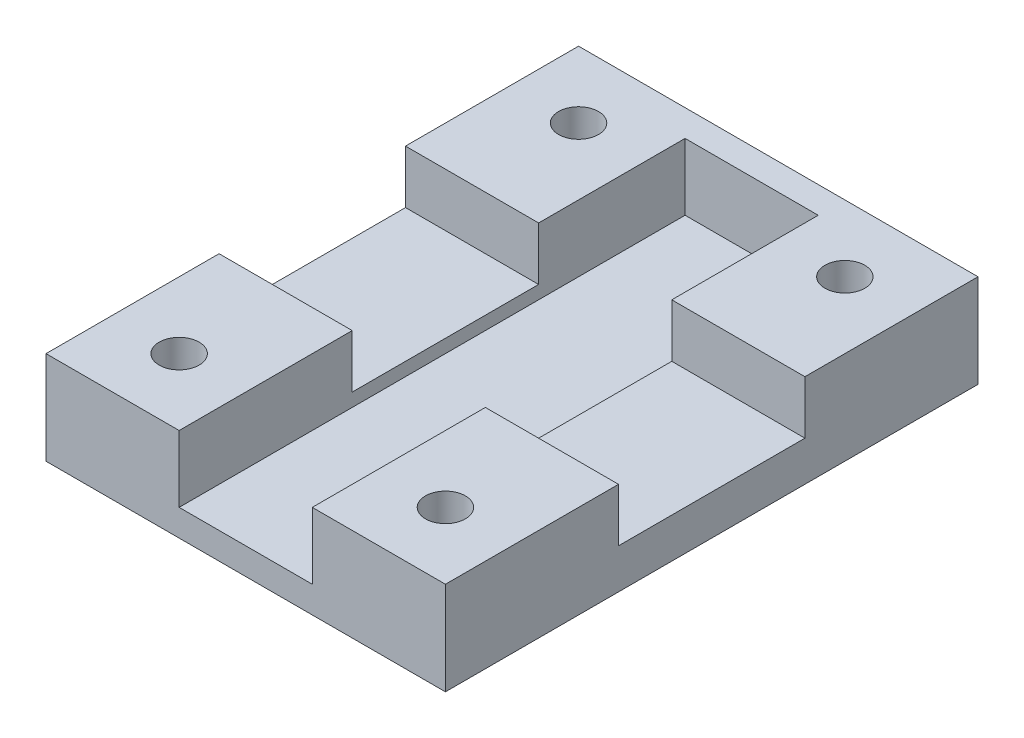
SolidWorks part; units mm, degrees
ref_plane "Plan de face" through (0, 0, 0) normal (0, 0, 1) x (1, 0, 0)
ref_plane "Plan de dessus" through (0, 0, 0) normal (0, 1, 0) x (1, 0, 0)
ref_plane "Plan de droite" through (0, 0, 0) normal (1, 0, 0) x (0, 0, -1)
sketch "Esquisse1" plane through (0, 0, 0) normal (0, 0, 1) x (1, 0, 0)
  line L0 (5, 0) -> (15, 0)
  line L1 (15, 0) -> (15, -7)
  line L2 (15, -7) -> (-15, -7)
  line L3 (-15, -7) -> (-15, 0)
  line L4 (-15, 0) -> (-5, 0)
  line L5 (5, 0) -> (5, -5)
  line L6 (5, -5) -> (-5, -5)
  line L7 (-5, -5) -> (-5, 0)
  dimension "D1" = 5
  dimension "D2" = 5
  dimension "D3" = 7
  dimension "D4" = 5
  dimension "D5" = 15
  dimension "D6" = 7
  dimension "D7" = 15
extrude "Boss.-Extru.1" add sketch "Esquisse1" along normal blind 40
sketch "Esquisse2" plane through (0, 0, 0) normal (0, 1, 0) x (1, 0, 0)
  line L0 (0, 0) -> (0, -40.0085) construction
  line L1 (-15, -20) -> (15, -20) construction
  line L2 (-15, -40) -> (-15, 0) construction
  line L3 (15, -40) -> (15, 0) construction
  circle A0 centre (-10, -5) radius 1.5
  circle A1 centre (-10, -35) radius 1.5
  circle A2 centre (10, -35) radius 1.5
  circle A3 centre (10, -5) radius 1.5
  dimension "D1" = 10
  dimension "D3" = 3
  dimension "D2" = 15
extrude "Enlèv. mat.-Extru.1" cut sketch "Esquisse2" against normal up to next
sketch "Esquisse3" plane through (0, 0, 0) normal (0, 1, 0) x (1, 0, 0)
  line L0 (0, 0) -> (0, -40) construction
  line L1 (5, -40) -> (-5, -40) construction
  line L2 (-15, -27) -> (-15, -13)
  line L3 (-15, -40) -> (-15, 0) construction
  line L4 (-15, -20) -> (15, -20) construction
  line L5 (15, -40) -> (15, 0) construction
  line L6 (-15, -13) -> (-5, -13)
  line L7 (-5, -40) -> (-5, 0) construction
  line L8 (-5, -13) -> (-5, -27)
  line L9 (-15, -27) -> (-5, -27)
  line L10 (15, -27) -> (5, -27)
  line L11 (5, -13) -> (5, -27)
  line L12 (15, -13) -> (5, -13)
  line L13 (15, -27) -> (15, -13)
  point P17 (-5, -20)
  dimension "D1" = 7
extrude "Enlèv. mat.-Extru.2" cut sketch "Esquisse3" against normal blind 4
sketch "Esquisse4" plane through (0, 0, 0) normal (0, 0, -1) x (-1, 0, 0)
  line L0 (-15, 0) -> (15, 0)
  line L1 (15, 0) -> (15, -7)
  line L2 (15, -7) -> (-15, -7)
  line L3 (-15, -7) -> (-15, 0)
extrude "Boss.-Extru.2" add sketch "Esquisse4" against normal blind 2
